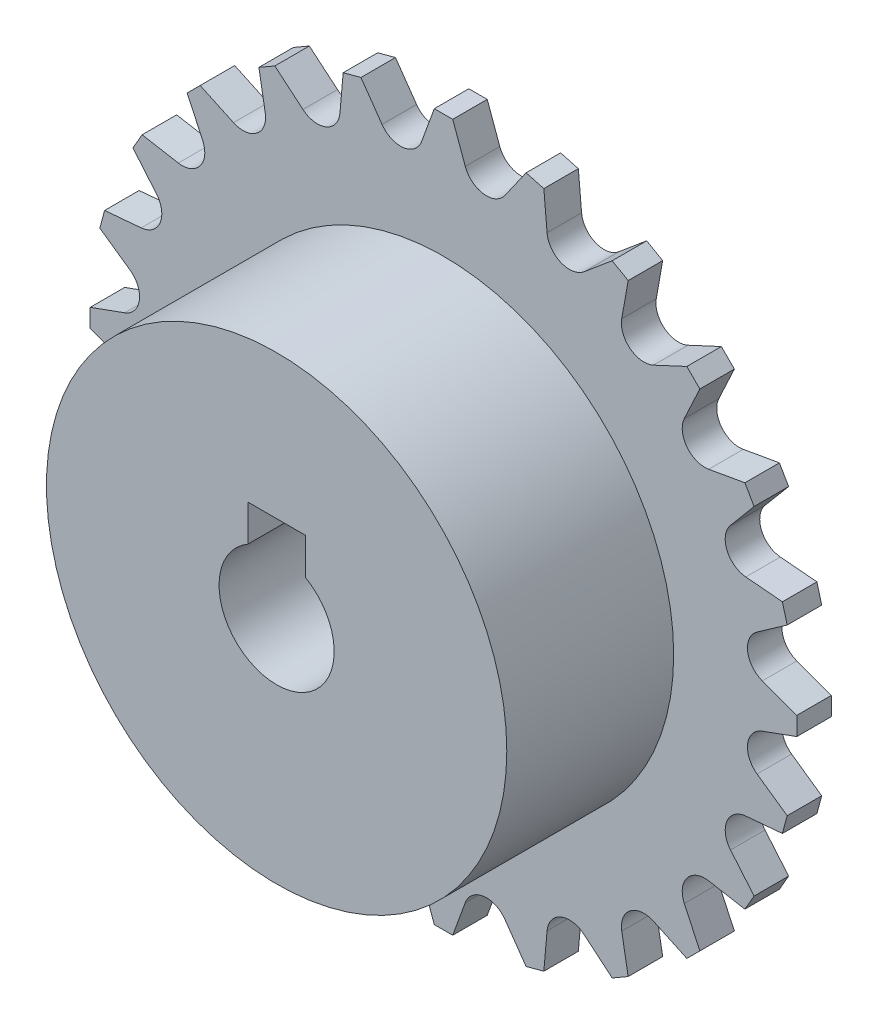
SolidWorks part; units mm, degrees
ref_plane "Front Plane" through (0, 0, 0) normal (0, 0, 1) x (1, 0, 0)
ref_plane "Top Plane" through (0, 0, 0) normal (0, 1, 0) x (1, 0, 0)
ref_plane "Right Plane" through (0, 0, 0) normal (1, 0, 0) x (0, 0, -1)
sketch "Sketch1" plane through (0, 0, 0) normal (0, 0, 1) x (1, 0, 0)
  line L0 (0, 9.525) -> (0, 6.35) construction
  line L2 (-3.175, 5.4993) -> (-3.175, 9.525)
  line L3 (-3.175, 9.525) -> (3.175, 9.525)
  line L4 (3.175, 5.4993) -> (3.175, 9.525)
  line L5 (-1.016, 38.989) -> (1.016, 38.989)
  line L10 (1.016, 38.989) -> (2.4027, 35.179)
  line L11 (0, 38.989) -> (0, 0) construction
  line L12 (-1.016, 38.989) -> (-2.4027, 35.179)
  line L13 (-2.4027, 35.179) -> (0, 0) construction
  line L14 (0, 0) -> (6.7841, 34.6022) construction
  line L84 (11.0725, 37.3975) -> (11.4259, 33.3584)
  line L85 (9.1097, 37.9234) -> (11.0725, 37.3975)
  line L86 (9.1097, 37.9234) -> (6.7841, 34.6022)
  line L87 (20.3744, 33.2575) -> (19.6703, 29.2645)
  line L88 (18.6146, 34.2735) -> (20.3744, 33.2575)
  line L89 (18.6146, 34.2735) -> (15.5087, 31.6673)
  line L90 (28.2878, 26.851) -> (26.5743, 23.1763)
  line L91 (26.851, 28.2878) -> (28.2878, 26.851)
  line L92 (26.851, 28.2878) -> (23.1763, 26.5743)
  line L93 (34.2735, 18.6146) -> (31.6673, 15.5087)
  line L94 (33.2575, 20.3744) -> (34.2735, 18.6146)
  line L95 (33.2575, 20.3744) -> (29.2645, 19.6703)
  line L96 (37.9234, 9.1097) -> (34.6022, 6.7841)
  line L97 (37.3975, 11.0725) -> (37.9234, 9.1097)
  line L98 (37.3975, 11.0725) -> (33.3584, 11.4259)
  line L99 (38.989, -1.016) -> (35.179, -2.4027)
  line L100 (38.989, 1.016) -> (38.989, -1.016)
  line L101 (38.989, 1.016) -> (35.179, 2.4027)
  line L102 (37.3975, -11.0725) -> (33.3584, -11.4259)
  line L103 (37.9234, -9.1097) -> (37.3975, -11.0725)
  line L104 (37.9234, -9.1097) -> (34.6022, -6.7841)
  line L105 (33.2575, -20.3744) -> (29.2645, -19.6703)
  line L106 (34.2735, -18.6146) -> (33.2575, -20.3744)
  line L107 (34.2735, -18.6146) -> (31.6673, -15.5087)
  line L108 (26.851, -28.2878) -> (23.1763, -26.5743)
  line L109 (28.2878, -26.851) -> (26.851, -28.2878)
  line L110 (28.2878, -26.851) -> (26.5743, -23.1763)
  line L111 (18.6146, -34.2735) -> (15.5087, -31.6673)
  line L112 (20.3744, -33.2575) -> (18.6146, -34.2735)
  line L113 (20.3744, -33.2575) -> (19.6703, -29.2645)
  line L114 (9.1097, -37.9234) -> (6.7841, -34.6022)
  line L115 (11.0725, -37.3975) -> (9.1097, -37.9234)
  line L116 (11.0725, -37.3975) -> (11.4259, -33.3584)
  line L117 (-1.016, -38.989) -> (-2.4027, -35.179)
  line L118 (1.016, -38.989) -> (-1.016, -38.989)
  line L119 (1.016, -38.989) -> (2.4027, -35.179)
  line L120 (-11.0725, -37.3975) -> (-11.4259, -33.3584)
  line L121 (-9.1097, -37.9234) -> (-11.0725, -37.3975)
  line L122 (-9.1097, -37.9234) -> (-6.7841, -34.6022)
  line L123 (-20.3744, -33.2575) -> (-19.6703, -29.2645)
  line L124 (-18.6146, -34.2735) -> (-20.3744, -33.2575)
  line L125 (-18.6146, -34.2735) -> (-15.5087, -31.6673)
  line L126 (-28.2878, -26.851) -> (-26.5743, -23.1763)
  line L127 (-26.851, -28.2878) -> (-28.2878, -26.851)
  line L128 (-26.851, -28.2878) -> (-23.1763, -26.5743)
  line L129 (-34.2735, -18.6146) -> (-31.6673, -15.5087)
  line L130 (-33.2575, -20.3744) -> (-34.2735, -18.6146)
  line L131 (-33.2575, -20.3744) -> (-29.2645, -19.6703)
  line L132 (-37.9234, -9.1097) -> (-34.6022, -6.7841)
  line L133 (-37.3975, -11.0725) -> (-37.9234, -9.1097)
  line L134 (-37.3975, -11.0725) -> (-33.3584, -11.4259)
  line L135 (-38.989, 1.016) -> (-35.179, 2.4027)
  line L136 (-38.989, -1.016) -> (-38.989, 1.016)
  line L137 (-38.989, -1.016) -> (-35.179, -2.4027)
  line L138 (-37.3975, 11.0725) -> (-33.3584, 11.4259)
  line L139 (-37.9234, 9.1097) -> (-37.3975, 11.0725)
  line L140 (-37.9234, 9.1097) -> (-34.6022, 6.7841)
  line L141 (-33.2575, 20.3744) -> (-29.2645, 19.6703)
  line L142 (-34.2735, 18.6146) -> (-33.2575, 20.3744)
  line L143 (-34.2735, 18.6146) -> (-31.6673, 15.5087)
  line L144 (-26.851, 28.2878) -> (-23.1763, 26.5743)
  line L145 (-28.2878, 26.851) -> (-26.851, 28.2878)
  line L146 (-28.2878, 26.851) -> (-26.5743, 23.1763)
  line L147 (-18.6146, 34.2735) -> (-15.5087, 31.6673)
  line L148 (-20.3744, 33.2575) -> (-18.6146, 34.2735)
  line L149 (-20.3744, 33.2575) -> (-19.6703, 29.2645)
  line L150 (-9.1097, 37.9234) -> (-6.7841, 34.6022)
  line L151 (-11.0725, 37.3975) -> (-9.1097, 37.9234)
  line L152 (-11.0725, 37.3975) -> (-11.4259, 33.3584)
  arc A0 (-3.175, 5.4993) -> (3.175, 5.4993) centre (0, 0) ccw
  circle A1 centre (0, 0) radius 25.4
  arc A2 (2.4027, 35.179) -> (6.7841, 34.6022) centre (4.7436, 36.031) ccw
  arc A3 (11.4259, 33.3584) -> (15.5087, 31.6673) centre (13.9074, 33.5755) ccw
  arc A4 (19.6703, 29.2645) -> (23.1763, 26.5743) centre (22.1236, 28.832) ccw
  arc A5 (26.5743, 23.1763) -> (29.2645, 19.6703) centre (28.832, 22.1236) ccw
  arc A6 (31.6673, 15.5087) -> (33.3584, 11.4259) centre (33.5755, 13.9074) ccw
  arc A7 (34.6022, 6.7841) -> (35.179, 2.4027) centre (36.031, 4.7436) ccw
  arc A8 (35.179, -2.4027) -> (34.6022, -6.7841) centre (36.031, -4.7436) ccw
  arc A9 (33.3584, -11.4259) -> (31.6673, -15.5087) centre (33.5755, -13.9074) ccw
  arc A10 (29.2645, -19.6703) -> (26.5743, -23.1763) centre (28.832, -22.1236) ccw
  arc A11 (23.1763, -26.5743) -> (19.6703, -29.2645) centre (22.1236, -28.832) ccw
  arc A12 (15.5087, -31.6673) -> (11.4259, -33.3584) centre (13.9074, -33.5755) ccw
  arc A13 (6.7841, -34.6022) -> (2.4027, -35.179) centre (4.7436, -36.031) ccw
  arc A14 (-2.4027, -35.179) -> (-6.7841, -34.6022) centre (-4.7436, -36.031) ccw
  arc A15 (-11.4259, -33.3584) -> (-15.5087, -31.6673) centre (-13.9074, -33.5755) ccw
  arc A16 (-19.6703, -29.2645) -> (-23.1763, -26.5743) centre (-22.1236, -28.832) ccw
  arc A17 (-26.5743, -23.1763) -> (-29.2645, -19.6703) centre (-28.832, -22.1236) ccw
  arc A18 (-31.6673, -15.5087) -> (-33.3584, -11.4259) centre (-33.5755, -13.9074) ccw
  arc A19 (-34.6022, -6.7841) -> (-35.179, -2.4027) centre (-36.031, -4.7436) ccw
  arc A20 (-35.179, 2.4027) -> (-34.6022, 6.7841) centre (-36.031, 4.7436) ccw
  arc A21 (-33.3584, 11.4259) -> (-31.6673, 15.5087) centre (-33.5755, 13.9074) ccw
  arc A22 (-29.2645, 19.6703) -> (-26.5743, 23.1763) centre (-28.832, 22.1236) ccw
  arc A23 (-23.1763, 26.5743) -> (-19.6703, 29.2645) centre (-22.1236, 28.832) ccw
  arc A24 (-15.5087, 31.6673) -> (-11.4259, 33.3584) centre (-13.9074, 33.5755) ccw
  arc A25 (-6.7841, 34.6022) -> (-2.4027, 35.179) centre (-4.7436, 36.031) ccw
  point P4 (0, 6.35)
  dimension "D2" = 12.7
  dimension "D1" = 50.8
  dimension "D3" = 6.35
  dimension "D4" = 3.175
  dimension "D5" = 2.032
  dimension "D6" = 110
  dimension "D7" = 3.81
  dimension "D9" = 15
  dimension "D8" = 38.989
  dimension "D10" = 24
extrude "Boss-Extrude1" add sketch "Sketch1" along normal blind 3.81 contours A25 L150 L151 L152 A24 L147 L148 L149 A23 L144 L145 L146 A22 L141 L142 L143 A21 L138 L139 L140 A20 L135 L136 L137 A19 L132 L133 L134 A18 L129 L130 L131 A17 L126 L127 L128 A16 L123 L124 L125 A15 L120 L121 L122 A14 L117 L118 L119 A13 L114 L115 region at (0, 37.8862, 0)
extrude "Boss-Extrude2" add sketch "Sketch1<3>" along normal blind 22.225 contours A1 A0 L2 L3 L4 region at (-24.6816, 0, 0)
sketch "Sketch1<3>" plane through (0, 0, 0) normal (0, 0, 1) x (1, 0, 0) same geometry as "Sketch1"
equation "\"Radius\"= 1.535"
equation "\"D8@Sketch1\" = \"Radius\""
